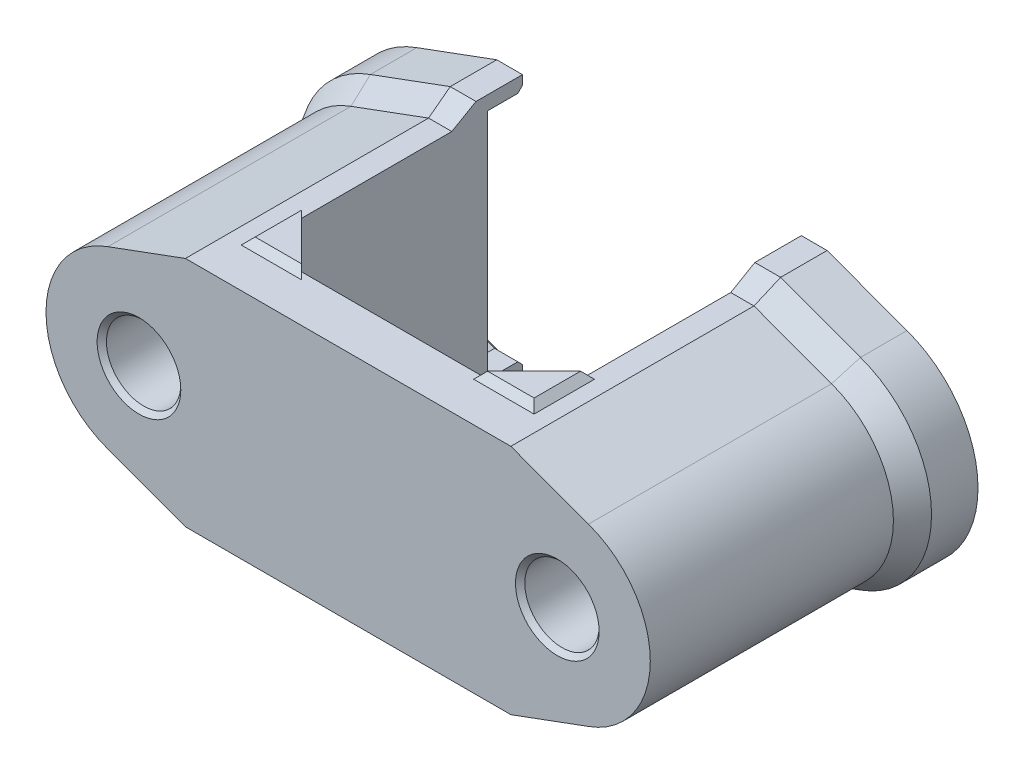
SolidWorks part; units mm, degrees
ref_plane "Ebene vorne" through (0, 0, 0) normal (0, 0, 1) x (1, 0, 0)
ref_plane "Ebene oben" through (0, 0, 0) normal (0, 1, 0) x (1, 0, 0)
ref_plane "Ebene rechts" through (0, 0, 0) normal (1, 0, 0) x (0, 0, -1)
sketch "Skizze2" plane through (0, 0, 0) normal (0, 0, 1) x (1, 0, 0)
  line L0 (0, 0) -> (0, 4.16) construction
  line L1 (9, 0) -> (-9, 0) construction
  line L2 (-6, -2.6458) -> (-6, -5)
  line L7 (6, 5) -> (-6, 5)
  line L8 (6, 5) -> (6, 2.6458)
  line L9 (6, -5) -> (-6, -5)
  line L10 (-6, 5) -> (-6, 2.6458)
  line L11 (6, 5) -> (-6, -5) construction
  line L12 (6, -5) -> (-6, 5) construction
  line L13 (6, -2.6458) -> (6, -5)
  circle A0 centre (-9, 0) radius 1.6
  arc A1 (-6, 2.6458) -> (-6, -2.6458) centre (-9, 0) ccw
  circle A2 centre (9, 0) radius 1.6
  arc A3 (6, 2.6458) -> (6, -2.6458) centre (9, 0) cw
  dimension "D1" = 3.2
  dimension "D2" = 8
  dimension "D3" = 18
  dimension "D4" = 10
  dimension "D5" = 12
extrude "Aufsatz-Linear austragen1" add sketch "Skizze2" along normal blind 12
ref_plane "Ebene1" through (0, 0, 0) normal (0, -1, 0) x (-1, 0, 0)
sketch "Skizze3" plane through (0, 0, 0) normal (0, -1, 0) x (-1, 0, 0)
  line L0 (6, 0) -> (-6, 0) construction
  line L1 (-6, 0) -> (6, 0)
  line L2 (-6, 0) -> (-6, -10)
  line L3 (-6, -10) -> (6, -10)
  line L4 (6, 0) -> (6, -10)
  line L5 (0, -10) -> (0, 0) construction
  dimension "D1" = 10
  dimension "D2" = 12
extrude "Schnitt-Linear austragen1" cut sketch "Skizze3" against normal through all and the other way through all
sketch "Skizze4" plane through (0, 0, 12) normal (0, 0, 1) x (1, 0, 0)
  line L0 (0, 5) -> (0, 0) construction
  line L1 (6, 5) -> (-6, 5) construction
  line L2 (-6, 5) -> (-7, 5)
  line L3 (-7, 5) -> (-10.3385, 3.7694)
  line L4 (-6, 5) -> (-6, 2.6458) construction
  line L5 (-6, 5) -> (-6, 2.6458)
  line L6 (-1.1, 0) -> (1.1, 0) construction
  line L7 (-6, -5) -> (-6, -2.6458)
  line L8 (-7, -5) -> (-10.3385, -3.7694)
  line L9 (-6, -5) -> (-7, -5)
  line L10 (6, -5) -> (7, -5)
  line L11 (7, -5) -> (10.3385, -3.7694)
  line L12 (6, -5) -> (6, -2.6458)
  line L13 (6, 5) -> (6, 2.6458)
  line L14 (7, 5) -> (10.3385, 3.7694)
  line L15 (6, 5) -> (7, 5)
  arc A0 (-6, 2.6458) -> (-6, -2.6458) centre (-9, 0) ccw construction
  arc A1 (-6, 2.6458) -> (-10.3385, 3.7694) centre (-9, 0) ccw
  arc A2 (-6, -2.6458) -> (-10.3385, -3.7694) centre (-9, 0) cw
  arc A3 (6, -2.6458) -> (10.3385, -3.7694) centre (9, 0) ccw
  arc A4 (6, 2.6458) -> (10.3385, 3.7694) centre (9, 0) cw
  arc M5 (-6, 2.6458) -> (-6, -2.6458) centre (-9, 0) ccw
  line M6 (-6, -2.6458) -> (-6, -5)
  line M8 (6, -5) -> (6, -2.6458)
  arc M9 (6, -2.6458) -> (6, 2.6458) centre (9, 0) ccw
  line M10 (6, 2.6458) -> (6, 5)
  line M12 (-6, 5) -> (-6, 2.6458)
  dimension "D1" = 1
extrude "Aufsatz-Linear austragen2" add sketch "Skizze4" against normal through all contours L2 L3 M5 M12 | L9 L8 M6 M5 | L15 L14 M10 M9 | L10 L11 M9 M8 region at (-7.1267, 4.1275, 12) region at (-7.1267, -4.1275, 12) region at (7.1267, -4.1275, 12) region at (7.1267, 4.1275, 12)
sketch "Skizze5" plane through (0, -5, 0) normal (0, -1, 0) x (1, 0, 0)
  line L0 (-6, 10) -> (-4, 10)
  line L1 (6, 10) -> (-6, 10) construction
  line L2 (-4, 10) -> (-6, 8)
  line L3 (-6, 0) -> (-6, 10) construction
  line L4 (-6, 8) -> (-6, 10)
  line L5 (0, 12) -> (0, 10) construction
  line L6 (-7, 12) -> (7, 12) construction
  line L7 (6, 8) -> (6, 10)
  line L8 (4, 10) -> (6, 8)
  line L9 (6, 10) -> (4, 10)
  dimension "D1" = 2
extrude "Aufsatz-Linear austragen3" add sketch "Skizze5" against normal blind 0.4 and the other way blind 0.3
mirror "Spiegeln1" about plane through (0, 0, 0) normal (0, -1, 0) of "Aufsatz-Linear austragen3"
chamfer "Fase3" distance 0.3 angle 45 8 edges at (6, -5, 9) (5, -5, 10) (-6, -5, 9) (-5, -5, 10) (6, 5, 9) (5, 5, 10) (-5, 5, 10) (-6, 5, 9)
ref_plane "Ebene2" through (0, 0, -1.5) normal (0, 0, -1) x (-1, 0, 0)
sketch "Skizze6" plane through (0, 0, -1.5) normal (0, 0, -1) x (-1, 0, 0)
  line L0 (6, -5) -> (7, -5) construction
  line L1 (7, -5) -> (10.3385, -3.7694) construction
  line L2 (7, 5) -> (10.3385, 3.7694) construction
  line L3 (6, 5) -> (7, 5) construction
  line L4 (6, -5) -> (7, -5)
  line L5 (7, -5) -> (10.3385, -3.7694)
  line L6 (7, 5) -> (10.3385, 3.7694)
  line L7 (6, 5) -> (7, 5)
  line L8 (6, 5.6) -> (7.1071, 5.6)
  line L9 (7.1071, 5.6) -> (10.5428, 4.3336)
  line L10 (7.1071, -5.6) -> (10.5428, -4.3336)
  line L11 (6, -5.6) -> (7.1071, -5.6)
  line L12 (6, 5.6) -> (6, 5)
  line L13 (6, -5) -> (6, -5.6)
  line L14 (0, 5) -> (0, -5) construction
  line L15 (-4, 5) -> (4, 5) construction
  line L16 (-4, -5) -> (4, -5) construction
  line L17 (-6, -5) -> (-6, -5.6)
  line L18 (-6, 5.6) -> (-6, 5)
  line L19 (-6, -5.6) -> (-7.1071, -5.6)
  line L20 (-7.1071, -5.6) -> (-10.5428, -4.3336)
  line L21 (-7.1071, 5.6) -> (-10.5428, 4.3336)
  line L22 (-6, 5.6) -> (-7.1071, 5.6)
  line L23 (-6, 5) -> (-7, 5)
  line L24 (-7, 5) -> (-10.3385, 3.7694)
  line L25 (-7, -5) -> (-10.3385, -3.7694)
  line L26 (-6, -5) -> (-7, -5)
  arc A0 (10.3385, -3.7694) -> (10.3385, 3.7694) centre (9, 0) ccw construction
  arc A1 (10.3385, -3.7694) -> (10.3385, 3.7694) centre (9, 0) ccw
  arc A2 (10.5428, -4.3336) -> (10.5428, 4.3336) centre (9, 0) ccw
  arc A3 (-10.5428, -4.3336) -> (-10.5428, 4.3336) centre (-9, 0) cw
  arc A4 (-10.3385, -3.7694) -> (-10.3385, 3.7694) centre (-9, 0) cw
  dimension "D1" = 0.6
extrude "Aufsatz-Linear austragen4" add sketch "Skizze6" against normal blind 2
chamfer "Fase1" distance 0.6 angle 60 9 edges at (-6.5, 5, 0.5) (-8.6692, 4.3847, 0.5) (-13, 0, 0.5) (-6.5, -5, 0.5) (-8.6692, -4.3847, 0.5) (6.5, -5, 0.5) (8.6692, -4.3847, 0.5) (8.6692, 4.3847, 0.5) (6.5, 5, 0.5) first distance on face at (-8.3079, 0, 0.5) first distance on face at (8.3079, 0, 0.5)
chamfer "Fase2" distance 0.2 angle 45 13 edges at (-6.5, -5, -1.5) (-8.6692, -4.3847, -1.5) (-8.6692, 4.3847, -1.5) (-6.5, 5, -1.5) (6.5, -5, -1.5) (8.6692, -4.3847, -1.5) (13, 0, -1.5) (8.6692, 4.3847, -1.5) (6.5, 5, -1.5) (-7.4, 0, 12) (7.4, 0, 12) (7.4, 0, 0) (-7.4, 0, 0)
